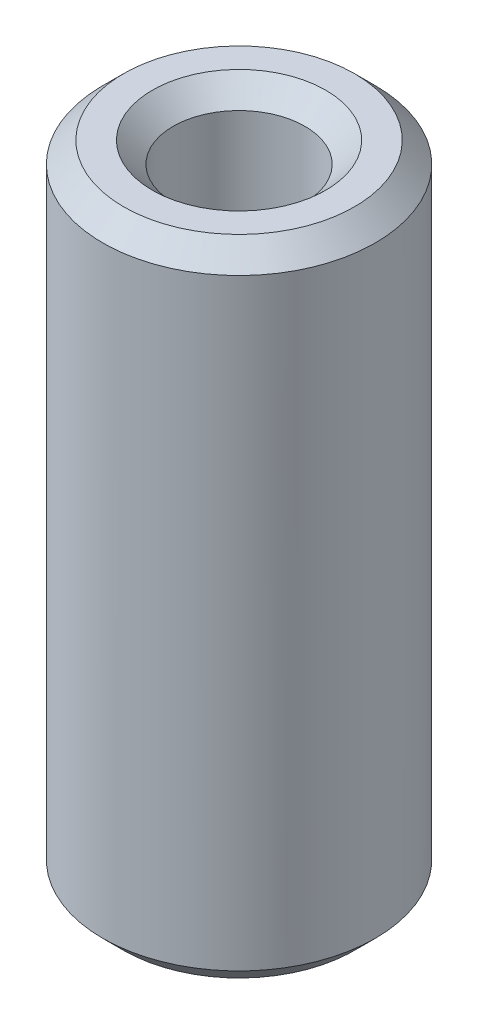
SolidWorks part; units mm, degrees
ref_plane "Front Plane" through (0, 0, 0) normal (0, 0, 1) x (1, 0, 0)
ref_plane "Top Plane" through (0, 0, 0) normal (0, 1, 0) x (1, 0, 0)
ref_plane "Right Plane" through (0, 0, 0) normal (1, 0, 0) x (0, 0, -1)
sketch "Sketch1" plane through (0, 0, 0) normal (0, 1, 0) x (1, 0, 0)
  circle A0 centre (0, 0) radius 5
  dimension "SLEEVE_OD" = 10
extrude "Boss-Extrude1" add sketch "Sketch1" along normal blind 23.6282
sketch "Sketch2" plane through (0, 0, 0) normal (0, 1, 0) x (1, 0, 0)
  circle A0 centre (0, 0) radius 2.4169
  dimension "BORE_D" = 4.8338
extrude "Cut-Extrude1" cut sketch "Sketch2" along normal through all
chamfer "Chamfer1" distance 0.765 angle 45 4 edges at (0, 23.6282, 2.4169) (0, 0, 2.4169) (0, 0, 5) (0, 23.6282, 5)
